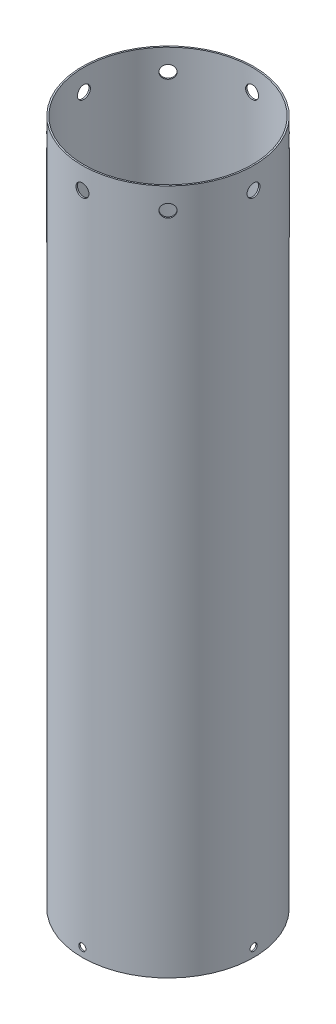
SolidWorks part; units mm, degrees
ref_plane "Front Plane" through (0, 0, 0) normal (0, 0, 1) x (1, 0, 0)
ref_plane "Top Plane" through (0, 0, 0) normal (0, 1, 0) x (1, 0, 0)
ref_plane "Right Plane" through (0, 0, 0) normal (1, 0, 0) x (0, 0, -1)
sketch "Sketch1" plane through (0, 0, 0) normal (0, 1, 0) x (1, 0, 0)
  circle A0 centre (0, 0) radius 76.2
  dimension "D1" = 152.4
extrude "Boss-Extrude1" add sketch "Sketch1" along normal blind 609.6
sketch "Sketch2" plane through (0, 609.6, 0) normal (0, 1, 0) x (1, 0, 0)
  circle A0 centre (0, 0) radius 74.93
  dimension "D1" = 149.86
extrude "Cut-Extrude1" cut sketch "Sketch2" against normal through all
sketch "Sketch3" plane through (0, 0, 0) normal (0, 0, 1) x (1, 0, 0)
  line L0 (0, 609.6) -> (0, 590.55)
  line L1 (76.2, 609.6) -> (-76.2, 609.6) construction
  circle A0 centre (0, 590.55) radius 5.715
extrude "Cut-Extrude2" cut sketch "Sketch3" against normal through all both and the other way through all contours A0
pattern_circular "CirPattern1" count 8 over 360 about axis through (0, 609.6, 0) along (0, -1, 0) of "Cut-Extrude2"
sketch "Sketch4" plane through (0, 0, 0) normal (0, 0, 1) x (1, 0, 0)
  line L0 (0, 0) -> (0, 7.9375)
  line L1 (-76.2, 0) -> (76.2, 0) construction
  circle A0 centre (0, 7.9375) radius 3.175
extrude "Cut-Extrude3" cut sketch "Sketch4" against normal through all both and the other way through all contours A0
pattern_circular "CirPattern2" count 4 over 360 about axis through (0, 609.6, 0) along (0, -1, 0) of "Cut-Extrude3" reverse direction yes
